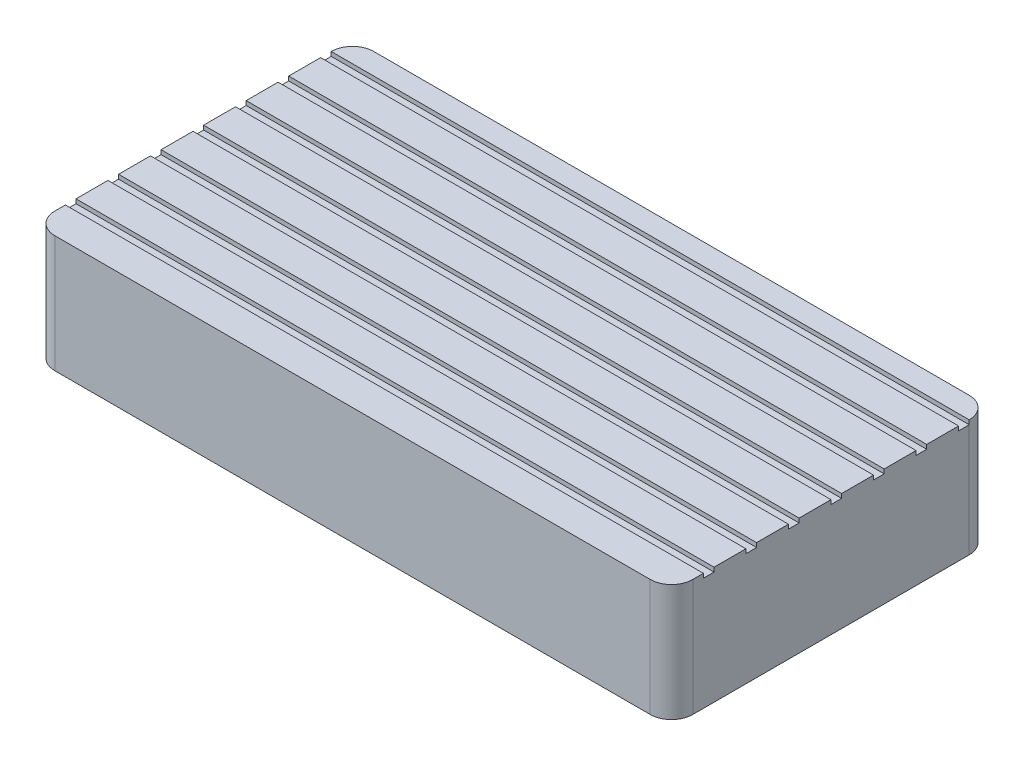
SolidWorks part; units mm, degrees
material "Copper"
ref_plane "Front Plane" through (0, 0, 0) normal (0, 0, 1) x (1, 0, 0)
ref_plane "Top Plane" through (0, 0, 0) normal (0, 1, 0) x (1, 0, 0)
ref_plane "Right Plane" through (0, 0, 0) normal (1, 0, 0) x (0, 0, -1)
sketch "Sketch1" plane through (0, 0, 0) normal (0, 1, 0) x (1, 0, 0)
  line L0 (-15, 0) -> (0, 0) construction
  line L1 (-15, -7.5) -> (15, -7.5)
  line L2 (-15, -7.5) -> (-15, 7.5)
  line L3 (-15, 7.5) -> (15, 7.5)
  line L4 (15, -7.5) -> (15, 7.5)
  line L5 (0, 0) -> (0, -7.5) construction
  dimension "D1" = 15
  dimension "D2" = 30
extrude "Boss-Extrude1" add sketch "Sketch1" along normal blind 5.5
sketch "Sketch2" plane through (0, 0, 0) normal (1, 0, 0) x (0, 0, -1)
  line L0 (-7.5, 5.5) -> (7.5, 5.5) construction
  line L1 (-6, 5.5) -> (-5.5, 5.5)
  line L2 (-6, 5.5) -> (-6, 5.3)
  line L3 (-6, 5.3) -> (-5.5, 5.3)
  line L4 (-5.5, 5.5) -> (-5.5, 5.3)
  line L5 (-7.5, 5.5) -> (-7.5, 0) construction
  line L6 (-3.5, 5.5) -> (-3.5, 5.3)
  line L7 (-4, 5.5) -> (-3.5, 5.5)
  line L8 (-4, 5.5) -> (-4, 5.3)
  line L9 (-4, 5.3) -> (-3.5, 5.3)
  line L10 (-1.5, 5.5) -> (-1.5, 5.3)
  line L11 (-2, 5.5) -> (-1.5, 5.5)
  line L12 (-2, 5.5) -> (-2, 5.3)
  line L13 (-2, 5.3) -> (-1.5, 5.3)
  line L14 (0.5, 5.5) -> (0.5, 5.3)
  line L15 (0, 5.5) -> (0.5, 5.5)
  line L16 (0, 5.5) -> (0, 5.3)
  line L17 (0, 5.3) -> (0.5, 5.3)
  line L18 (2.5, 5.5) -> (2.5, 5.3)
  line L19 (2, 5.5) -> (2.5, 5.5)
  line L20 (2, 5.5) -> (2, 5.3)
  line L21 (2, 5.3) -> (2.5, 5.3)
  line L22 (4.5, 5.5) -> (4.5, 5.3)
  line L23 (4, 5.5) -> (4.5, 5.5)
  line L24 (4, 5.5) -> (4, 5.3)
  line L25 (4, 5.3) -> (4.5, 5.3)
  line L26 (6.5, 5.5) -> (6.5, 5.3)
  line L27 (6, 5.5) -> (6.5, 5.5)
  line L28 (6, 5.5) -> (6, 5.3)
  line L29 (6, 5.3) -> (6.5, 5.3)
  dimension "D1" = 0.2
  dimension "D2" = 0.5
  dimension "D3" = 1.5
  dimension "D5" = 1.5
  dimension "D4" = 7
extrude "Cut-Extrude2" cut sketch "Sketch2" against normal through all both and the other way through all
ref_plane "Plane1" [suppressed] through (0, 0, 4) normal (0, 0, 1) x (1, 0, 0)
sketch "Sketch8" [suppressed] plane through (0, 0, 4) normal (0, 0, 1) x (1, 0, 0)
  line L0 (10.25, 0) -> (10.25, 3)
  line L1 (-15, 0) -> (15, 0) construction
  line L2 (10.25, 3) -> (9, 3.7217)
  line L3 (9, 3.7217) -> (9, 0)
  line L4 (9, 0) -> (10.25, 0)
  line L5 (0, 0) -> (0, 7.2512) construction
  line L6 (9, 0) -> (9, 5.5) construction
  line L7 (-15, 5.5) -> (15, 5.5) construction
  dimension "D1" = 18
  dimension "D2" = 2.5
  dimension "D3" = 3
  dimension "D4" = 60
revolve "Cut-Revolve1" [suppressed] cut sketch "Sketch8" angle 360 about L6
mirror "Mirror1" [suppressed] about plane through (0, 0, 0) normal (0, 0, 1)
mirror "Mirror2" [suppressed] about plane through (0, 0, 0) normal (1, 0, 0)
sketch "Sketch5" plane through (-15, 0, 0) normal (1, 0, 0) x (0, 0, -1)
  line L0 (-7.5, 0) -> (7.5, 0) construction
  line L1 (4.1, 0) -> (-5.1, 0)
  line L2 (4.1, 0) -> (4.1, 5.5)
  line L3 (4.1, 5.5) -> (-5.1, 5.5)
  line L4 (-5.1, 0) -> (-5.1, 5.5)
  line L5 (-3.5, 5.5) -> (-2, 5.5) construction
  line L6 (7.5, 0) -> (-7.5, 0) construction
  line L7 (-0.5, 0) -> (-0.5, 5.5) construction
  dimension "D1" = 9.2
  dimension "D2" = 0.5
extrude "Cut-Extrude4" [suppressed] cut sketch "Sketch5" along normal blind 1.6
sketch "Sketch9" plane through (0, 0, 0) normal (0, 0, 1) x (1, 0, 0)
  line L0 (-15, 2.5) -> (-7.6783, 2.5)
  line L1 (-15, 5.5) -> (-15, 0) construction
  line L2 (-7.6783, 2.5) -> (-8.4, 3.75)
  line L3 (-8.4, 3.75) -> (-15, 3.75)
  line L4 (-15, 3.75) -> (-15, 2.5)
  line L5 (-15, 2.5) -> (-16.9854, 2.5) construction
  line L6 (15, 0) -> (-15, 0) construction
  dimension "D1" = 2.5
  dimension "D2" = 6.6
  dimension "D3" = 60
  dimension "D4" = 2.5
revolve "Cut-Revolve2" [suppressed] cut sketch "Sketch9" angle 360 about L5
sketch "Sketch7" plane through (0, 0, 0) normal (0, -1, 0) x (1, 0, 0)
  line L0 (17.59, 0) -> (0, 0) construction
  circle A0 centre (17.59, 0) radius 6.5
  dimension "D1" = 13
  dimension "D2" = 17.59
extrude "Cut-Extrude6" [suppressed] cut sketch "Sketch7" against normal blind 1.75
fillet "Fillet1" radius 1 4 edges at (-15, 2.75, 7.5) (-15, 2.75, -7.5) (15, 2.75, -7.5) (15, 2.75, 7.5)
